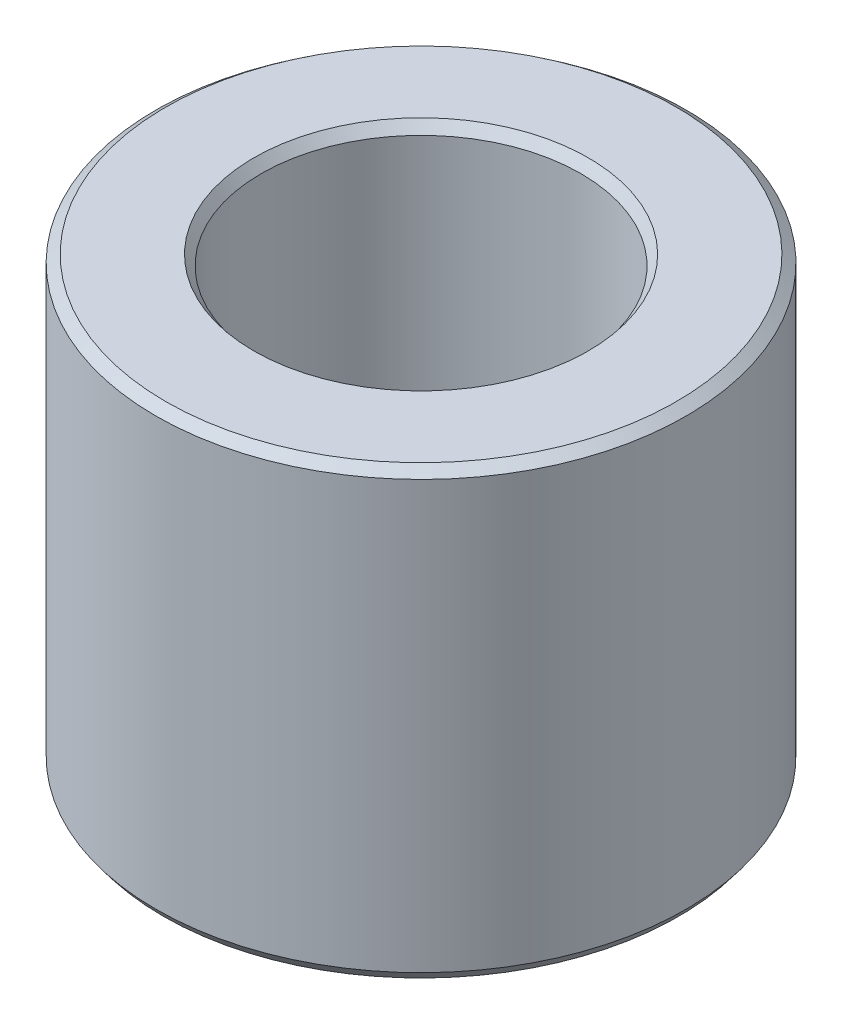
SolidWorks part; units mm, degrees
ref_plane "Front Plane" through (0, 0, 0) normal (0, 0, 1) x (1, 0, 0)
ref_plane "Top Plane" through (0, 0, 0) normal (0, 1, 0) x (1, 0, 0)
ref_plane "Right Plane" through (0, 0, 0) normal (1, 0, 0) x (0, 0, -1)
sketch "Sketch1" plane through (0, 0, 0) normal (0, 1, 0) x (1, 0, 0)
  circle A0 centre (0, 0) radius 52.5
  dimension "SLEEVE_OD" = 105
extrude "Boss-Extrude1" add sketch "Sketch1" along normal blind 88.0327
sketch "Sketch2" plane through (0, 0, 0) normal (0, 1, 0) x (1, 0, 0)
  circle A0 centre (0, 0) radius 31.6466
  dimension "BORE_D" = 63.2931
extrude "Cut-Extrude1" cut sketch "Sketch2" along normal through all
chamfer "Chamfer1" distance 1.4832 angle 52.983 4 edges at (0, 88.0327, 31.6466) (0, 0, 31.6466) (0, 0, 52.5) (0, 88.0327, 52.5) first distance on face at (0, 88.0327, 31.6466) first distance on face at (0, 0, 31.6466) first distance on face at (0, 88.0327, 52.5)
